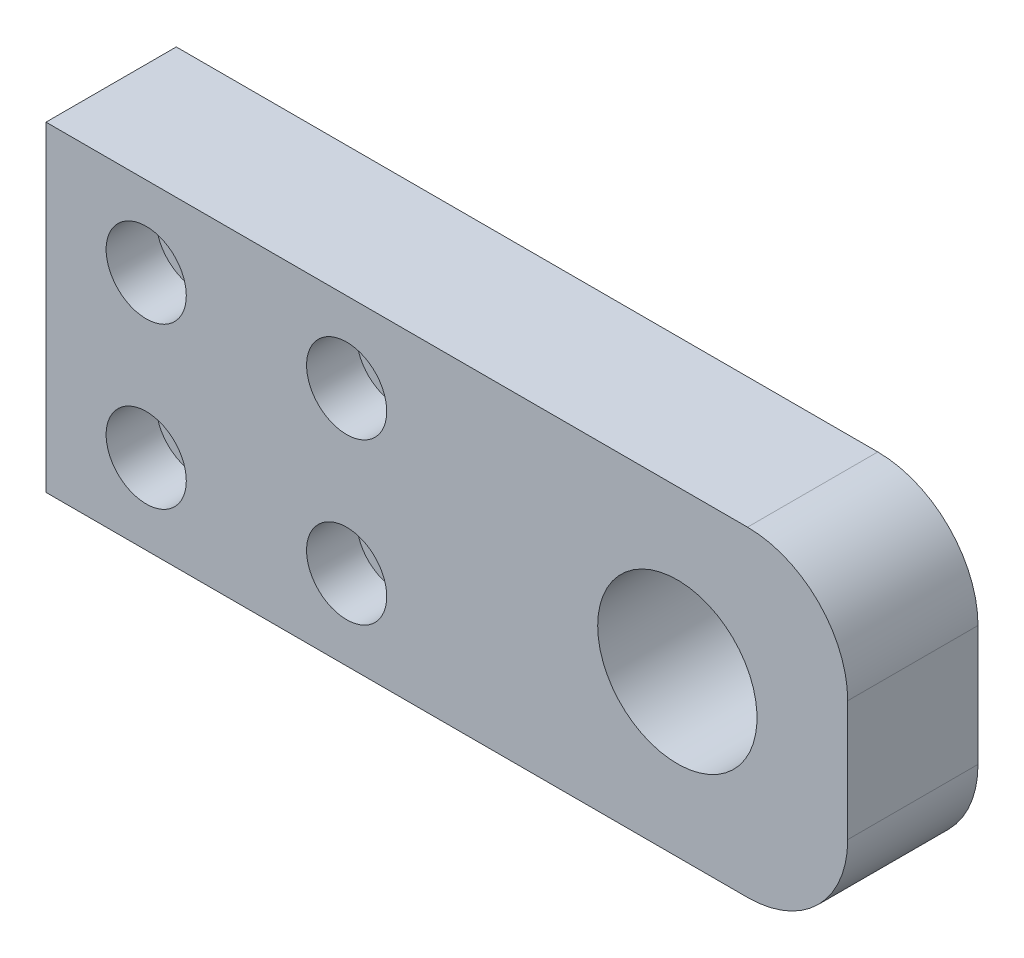
SolidWorks part; units mm, degrees
ref_plane "Alzado" through (0, 0, 0) normal (0, 0, 1) x (1, 0, 0)
ref_plane "Planta" through (0, 0, 0) normal (0, 1, 0) x (1, 0, 0)
ref_plane "Vista lateral" through (0, 0, 0) normal (1, 0, 0) x (0, 0, -1)
sketch "Croquis1" plane through (0, 0, 0) normal (0, 0, 1) x (1, 0, 0)
  line L0 (-10, -240) -> (-10, 0) construction
  line L1 (-10, -68) -> (70, -68)
  line L2 (-10, -68) -> (-10, -36)
  line L3 (-10, -36) -> (70, -36)
  line L4 (70, -68) -> (70, -36)
  line L5 (53, -52) -> (70, -52) construction
  circle A0 centre (53, -52) radius 7.95
  dimension "D1" = 15.9
  dimension "D2" = 32
  dimension "D3" = 80
extrude "Saliente-Extruir1" add sketch "Croquis1" along normal blind 13
sketch "Croquis2" plane through (0, 0, 13) normal (0, 0, 1) x (1, 0, 0)
  line L0 (-10, -52) -> (70, -52) construction
  line L1 (-10, -36) -> (-10, -68) construction
  line L2 (70, -68) -> (70, -36) construction
  circle A0 centre (0, -44) radius 2.05
  circle A1 centre (20, -44) radius 2.05
  circle A2 centre (0, -60) radius 2.05
  circle A3 centre (20, -60) radius 2.05
  dimension "D1" = 4.1
  dimension "D2" = 10
  dimension "D3" = 20
  dimension "D4" = 16
extrude "Cortar-Extruir1" cut sketch "Croquis2" against normal up to next
sketch "Croquis3" plane through (0, 0, 13) normal (0, 0, 1) x (1, 0, 0)
  circle A0 centre (0, -44) radius 4
  circle A1 centre (20, -44) radius 4
  circle A2 centre (20, -60) radius 4
  circle A3 centre (0, -60) radius 4
  dimension "D1" = 8
extrude "Cortar-Extruir2" cut sketch "Croquis3" against normal blind 5
fillet "Redondeo1" radius 10 2 edges at (70, -68, 6.5) (70, -36, 6.5)
sketch "Croquis4" plane through (0, 0, 0) normal (0, 0, -1) x (-1, 0, 0)
  line L0 (-30, -44) -> (-30, -60) construction
  line L3 (10, -36) -> (10, -68) construction
  line L4 (10, -68) -> (-60, -68) construction
  line L5 (-30, -44) -> (-35, -44)
  line L6 (-30, -44) -> (-30, -60)
  line L7 (-30, -60) -> (-35, -60)
  line L8 (-35, -44) -> (-35, -60)
  line L9 (-60, -36) -> (10, -36) construction
  dimension "D1" = 40
  dimension "D2" = 5
  dimension "D3" = 8
  dimension "D4" = 8
extrude "Saliente-Extruir2" add sketch "Croquis4" along normal blind 5
fillet "Redondeo2" radius 8 1 edges at (35, -52, 0)
